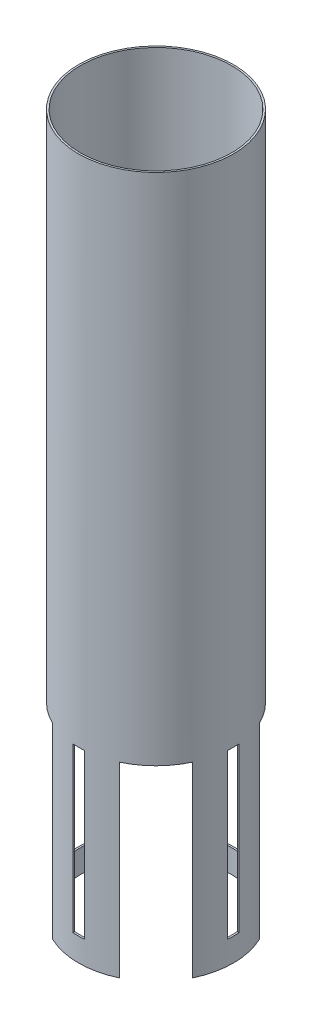
SolidWorks part; units mm, degrees
ref_plane "Front Plane" through (0, 0, 0) normal (0, 0, 1) x (1, 0, 0)
ref_plane "Top Plane" through (0, 0, 0) normal (0, 1, 0) x (1, 0, 0)
ref_plane "Right Plane" through (0, 0, 0) normal (1, 0, 0) x (0, 0, -1)
sketch "Sketch1" plane through (0, 0, 0) normal (0, 1, 0) x (1, 0, 0)
  circle A0 centre (0, 0) radius 33.16
  circle A1 centre (0, 0) radius 32.385
  dimension "D1" = 66.32
  dimension "D2" = 64.77
extrude "Boss-Extrude1" add sketch "Sketch1" along normal mid plane 300
sketch "Sketch2" plane through (0, 0, 0) normal (0, 0, 1) x (1, 0, 0)
  line L0 (-33.16, -150) -> (33.16, -150) construction
  line L1 (-2.5, -140) -> (2.5, -140)
  line L2 (-2.5, -140) -> (-2.5, -70)
  line L3 (-2.5, -70) -> (2.5, -70)
  line L4 (2.5, -140) -> (2.5, -70)
  line L5 (-2.5, -140) -> (2.5, -70) construction
  line L6 (-2.5, -70) -> (2.5, -140) construction
  point P0 (0, -105)
  dimension "D1" = 5
  dimension "D2" = 70
  dimension "D3" = 10
extrude "Cut-Extrude1" cut sketch "Sketch2" against normal through all
pattern_circular "CirPattern1" count 4 over 360 about axis through (0, 150, 0) along (0, -1, 0) of "Cut-Extrude1" reverse direction yes
ref_plane "Plane1" through (14.8942, 0, 14.8942) normal (-0.7071, 0, -0.7071) x (-0.7071, 0, 0.7071)
sketch "Sketch3" plane through (14.8942, 0, 14.8942) normal (-0.7071, 0, -0.7071) x (-0.7071, 0, 0.7071)
  line L0 (-33.16, -150) -> (33.16, -150) construction
  line L1 (-11, -70) -> (11, -70)
  line L2 (-11, -70) -> (-11, -150)
  line L3 (-11, -150) -> (11, -150)
  line L4 (11, -70) -> (11, -150)
  line L5 (-11, -70) -> (11, -150) construction
  line L6 (-11, -150) -> (11, -70) construction
  point P0 (0, -110)
  point P7 (0, 0)
  dimension "D1" = 80
  dimension "D2" = 22
extrude "Cut-Extrude2" cut sketch "Sketch3" against normal through all
pattern_circular "CirPattern2" count 4 over 360 about axis through (0, 150, 0) along (0, -1, 0) of "Cut-Extrude2"
